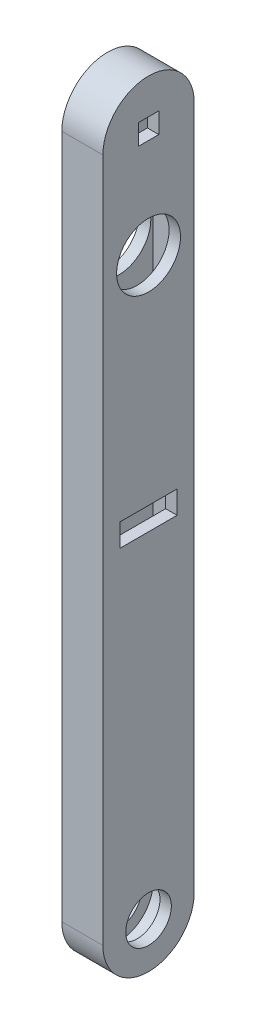
SolidWorks part; units mm, degrees
ref_plane "Front Plane" through (0, 0, 0) normal (0, 0, 1) x (1, 0, 0)
ref_plane "Top Plane" through (0, 0, 0) normal (0, 1, 0) x (1, 0, 0)
ref_plane "Right Plane" through (0, 0, 0) normal (1, 0, 0) x (0, 0, -1)
sketch "Sketch2" plane through (0, 0, 0) normal (1, 0, 0) x (0, 0, -1)
  line L0 (-20, 0) -> (20, 0) construction
  line L1 (-20, 48) -> (-20, -252)
  line L2 (20, 48) -> (20, -252)
  line L3 (0, 0) -> (0, 48) construction
  line L4 (20, 48) -> (-20, 48) construction
  line L5 (-4.5, 43.5) -> (4.5, 43.5)
  line L6 (-4.5, 43.5) -> (-4.5, 52.5)
  line L7 (-4.5, 52.5) -> (4.5, 52.5)
  line L8 (4.5, 43.5) -> (4.5, 52.5)
  line L9 (-4.5, 43.5) -> (4.5, 52.5) construction
  line L10 (-4.5, 52.5) -> (4.5, 43.5) construction
  line L11 (-20, -252) -> (20, -252) construction
  line L12 (0, 0) -> (0, -150) construction
  line L13 (15, 48) -> (15, -252)
  line L14 (-15, 48) -> (-15, -252)
  circle A0 centre (0, 0) radius 14
  arc A1 (-20, 48) -> (20, 48) centre (0, 48) cw
  circle A2 centre (0, -150) radius 10
  arc A3 (-20, -252) -> (20, -252) centre (0, -252) ccw
  circle A4 centre (0, -252) radius 10
  arc A5 (-15, -252) -> (15, -252) centre (0, -252) ccw
  arc A6 (-15, 48) -> (15, 48) centre (0, 48) cw
  dimension "D1" = 28
  dimension "D7" = 20
  dimension "D8" = 20
  dimension "D2" = 40
  dimension "D3" = 48
  dimension "D4" = 9
  dimension "D5" = 300
  dimension "D6" = 150
  dimension "D9" = 5
sketch "Sketch3" plane through (0, 0, 0) normal (0, 0, 1) x (1, 0, 0)
  line L0 (-145.1347, 0) -> (145.1347, 0) construction
  line L1 (0, -164.4063) -> (0, 164.4063) construction
  line L2 (0, 48) -> (0, -252) construction
  point P3 (-4, 0)
  point P7 (-9, 0)
  point P9 (0, 0)
  point P10 (0, 0)
  point P11 (0, 0)
  point P12 (0, 0)
  dimension "D1" = 18
  dimension "D2" = 5
extrude "Boss-Extrude1" add sketch "Sketch2" along normal up to vertex (-4 mm away) from vertex contours L1 A3 L2 A1 L14 A6 L13 A5 | A6 L14 A5 L13 A4 L8 L5 L6 L7 A0 A2 | A2 region at (0, 64.5766, 0) region at (0, -103.5215, 0) region at (0, -150, 0) up to point (-4, 0, 0) starting at point (-9, 0, 0)
extrude "Boss-Extrude2" add sketch "Sketch2<6>" along normal up to surface from vertex contours L1 A3 L2 A1 L14 A6 L13 A5 region at (0, 64.5766, 0) up to plane "Right Plane" starting at point (-4, 0, 0)
sketch "Sketch2<6>" plane through (0, 0, 0) normal (1, 0, 0) x (0, 0, -1) same geometry as "Sketch2"
mirror "Mirror1" about plane through (0, 0, 0) normal (1, 0, 0) of bodies 103
sketch "Sketch4" plane through (0, 0, 0) normal (1, 0, 0) x (0, 0, -1)
  line L0 (0, 0) -> (0, -150) construction
  line L1 (-12.5, -105) -> (12.5, -105)
  line L2 (-12.5, -105) -> (-12.5, -95)
  line L3 (-12.5, -95) -> (12.5, -95)
  line L4 (12.5, -105) -> (12.5, -95)
  line L5 (-12.5, -105) -> (12.5, -95) construction
  line L6 (-12.5, -95) -> (12.5, -105) construction
  point P0 (0, -100)
  point P7 (0, -55.0712)
  dimension "D1" = 10
  dimension "D2" = 45
  dimension "D3" = 25
extrude "Cut-Extrude1" cut sketch "Sketch4" against normal up to next from surface starting at face at (9, -102, 0)
